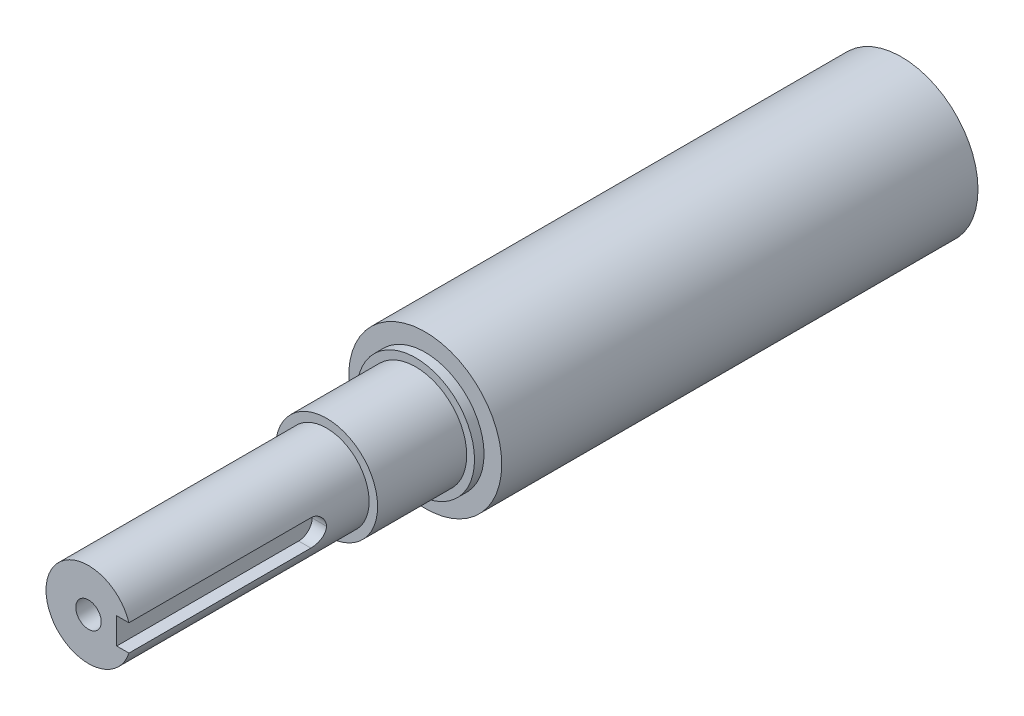
SolidWorks part; units mm, degrees
ref_plane "Front Plane" through (0, 0, 0) normal (0, 0, 1) x (1, 0, 0)
ref_plane "Top Plane" through (0, 0, 0) normal (0, 1, 0) x (1, 0, 0)
ref_plane "Right Plane" through (0, 0, 0) normal (1, 0, 0) x (0, 0, -1)
sketch "Sketch1" plane through (0, 0, 0) normal (0, 0, 1) x (1, 0, 0)
  line L0 (0, 0) -> (15.1868, 0) construction
  line L1 (7.5496, 2.4511) -> (5.2705, 2.4511)
  line L2 (5.2705, 2.4511) -> (5.2705, -2.4511)
  line L3 (7.5496, -2.4511) -> (5.2705, -2.4511)
  circle A0 centre (0, 0) radius 7.9375
  circle A1 centre (0, 0) radius 2.3749
  circle A2 centre (0, 0) radius 9.525
  circle A3 centre (0, 0) radius 10.9855
  circle A4 centre (0, 0) radius 14.2875
  point P10 (5.2705, 0)
  dimension "D1" = 15.875
  dimension "D2" = 4.7498
  dimension "D5" = 19.05
  dimension "D6" = 21.971
  dimension "D7" = 28.575
  dimension "D3" = 2.4511
  dimension "D4" = 5.2705
extrude "Boss-Extrude1" add sketch "Sketch1" along normal blind 61.087 contours A1 L2 L1 A0 L3 | L0 L2 L3 A0 | L2 L0 A0 L1 region at (6.5426, -1.1945, 0) region at (6.5426, 1.1945, 0) region at (5.0487, -1.2255, 0)
extrude "Boss-Extrude2" add sketch "Sketch1<4>" along normal blind 16.637 contours A0 A2 region at (-9.2556, 0, 0)
sketch "Sketch1<4>" plane through (0, 0, 0) normal (0, 0, 1) x (1, 0, 0) same geometry as "Sketch1"
extrude "Boss-Extrude3" add sketch "Sketch1<5>" against normal blind 90.7034 separate body contours A2 A3 region at (-10.6748, 0, 0)
sketch "Sketch1<5>" plane through (0, 0, 0) normal (0, 0, 1) x (1, 0, 0) same geometry as "Sketch1"
extrude "Boss-Extrude4" add sketch "Sketch1<7>" against normal blind 92.4052 contours A1 L2 L1 A0 L3 | L2 L0 A0 L1 | L0 L2 L3 A0 | A0 A2 region at (-9.2556, 0, 0) region at (6.5426, -1.1945, 0) region at (6.5426, 1.1945, 0) region at (5.0487, -1.2255, 0)
sketch "Sketch1<7>" plane through (0, 0, 0) normal (0, 0, 1) x (1, 0, 0) same geometry as "Sketch1"
extrude "Boss-Extrude5" add sketch "Sketch1<9>" against normal blind 90.7034 contours A3 A4 region at (-13.8834, 0, 0)
sketch "Sketch1<9>" plane through (0, 0, 0) normal (0, 0, 1) x (1, 0, 0) same geometry as "Sketch1"
extrude "Cut-Extrude1" cut sketch "Sketch1<10>" against normal blind 1.778 contours A3 A4 region at (-13.8834, 0, 0)
sketch "Sketch1<10>" plane through (0, 0, 0) normal (0, 0, 1) x (1, 0, 0) same geometry as "Sketch1"
extrude "Cut-Extrude2" cut sketch "Sketch1<13>" along normal blind 66.294 contours L2 L0 A0 L1 | L0 L2 L3 A0 region at (6.5426, -1.1945, 0) region at (6.5426, 1.1945, 0)
sketch "Sketch1<13>" plane through (0, 0, 0) normal (0, 0, 1) x (1, 0, 0) same geometry as "Sketch1"
extrude "Boss-Extrude6" add sketch "Sketch1<14>" along normal blind 24.5872 contours L2 L0 A0 L1 | L0 L2 L3 A0 region at (6.5426, -1.1945, 0) region at (6.5426, 1.1945, 0)
sketch "Sketch1<14>" plane through (0, 0, 0) normal (0, 0, 1) x (1, 0, 0) same geometry as "Sketch1"
fillet "Fillet2" radius 2.54 2 edges at (6.41, -2.4511, 24.5872) (6.41, 2.4511, 24.5872)
extrude "Boss-Extrude7" add sketch "Sketch1<15>" along normal blind 53.467 and the other way blind 71.0692 contours A1 region at (0, 0, 0)
sketch "Sketch1<15>" plane through (0, 0, 0) normal (0, 0, 1) x (1, 0, 0) same geometry as "Sketch1"
fillet "Fillet3" radius 2.286 1 edges at (2.3749, 0, 53.467)
fillet "Fillet4" radius 2.286 1 edges at (2.3749, 0, -71.0692)
